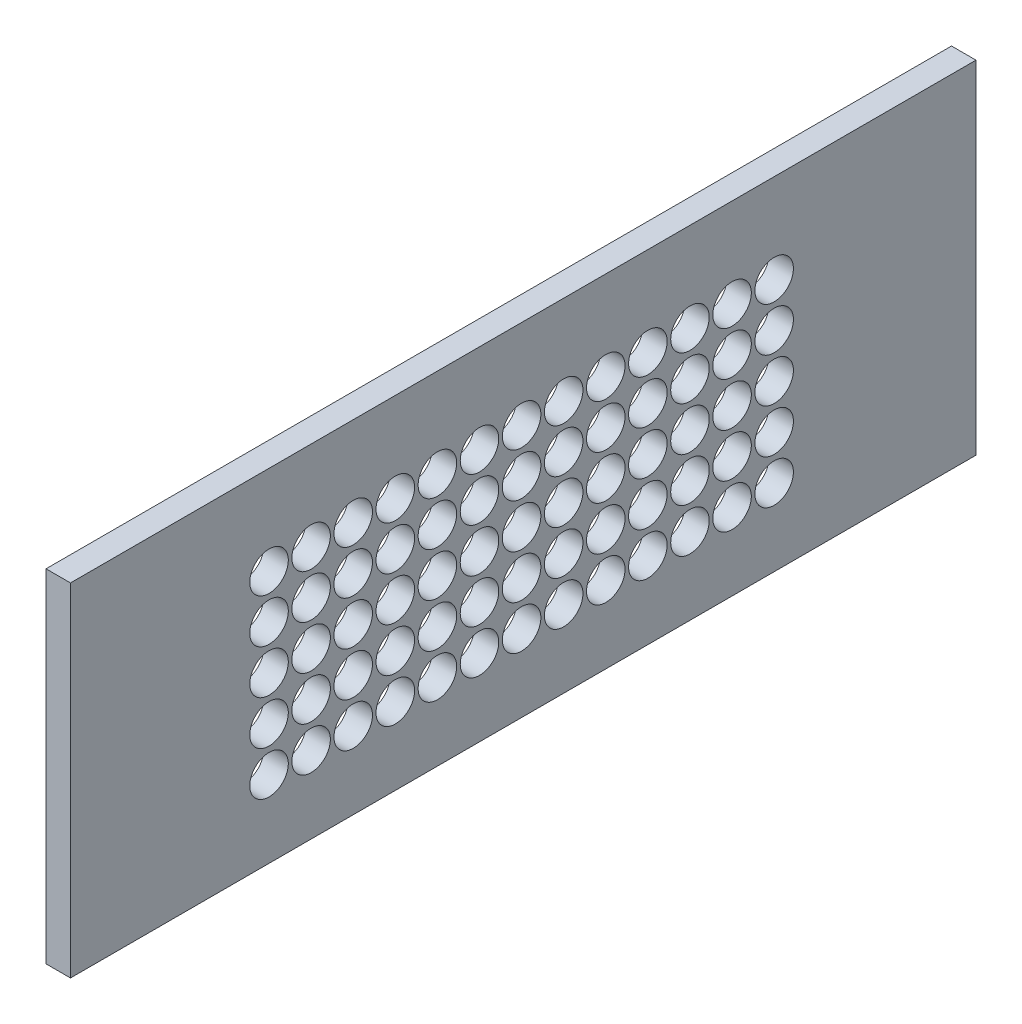
SolidWorks part; units mm, degrees
material "ABS PC"
ref_plane "X-Y Datum" through (0, 0, 0) normal (0, 0, 1) x (1, 0, 0)
ref_plane "X-Z Datum" through (0, 0, 0) normal (0, 1, 0) x (1, 0, 0)
ref_plane "Y-Z Datum" through (0, 0, 0) normal (1, 0, 0) x (0, 0, -1)
sketch "Sketch1" plane through (0, 0, 0) normal (0, 0, 1) x (1, 0, 0)
  line L1 (-3.175, -44.3878) -> (3.175, -44.3878)
  line L2 (-3.175, -44.3878) -> (-3.175, 44.3878)
  line L3 (-3.175, 44.3878) -> (3.175, 44.3878)
  line L4 (3.175, -44.3878) -> (3.175, 44.3878)
  line L5 (-3.175, -44.3878) -> (3.175, 44.3878) construction
  line L6 (-3.175, 44.3878) -> (3.175, -44.3878) construction
  point P0 (0, 0)
  dimension "D1" = 88.7755
  dimension "D2" = 6.35
extrude "Boss-Extrude1" add sketch "Sketch1" along normal blind 234.95
ref_plane "Plane1" through (104.775, -38.0378, 25.4) normal (0, 1, 0) x (1, 0, 0)
sketch "Sketch3" plane through (-3.175, 0, 0) normal (-1, 0, 0) x (0, 0, 1)
  circle A0 centre (52.3692, 21.2622) radius 5 construction
  circle A1 centre (52.3692, 21.2622) radius 5
extrude "Cut-Extrude1" cut sketch "Sketch3" against normal through all
pattern_linear "LPattern1" count 5 spacing 11.43 along (0, -1, 0) count 13 spacing 10.922 along (0, 0, 1) of "Cut-Extrude1"
